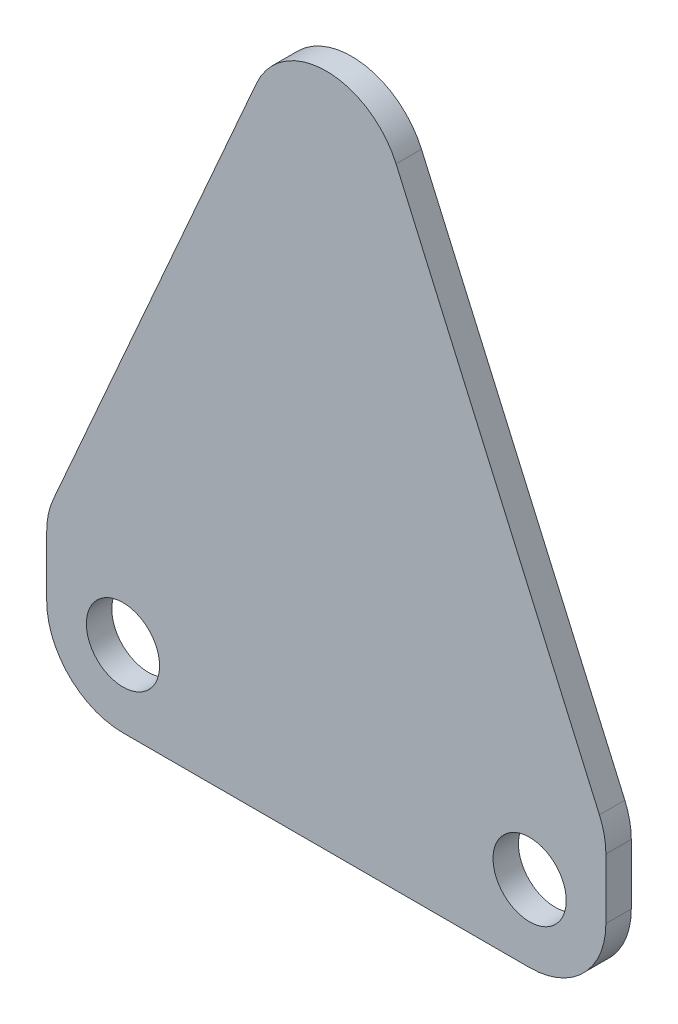
SolidWorks part; units mm, degrees
ref_plane "Front Plane" through (0, 0, 0) normal (0, 0, 1) x (1, 0, 0)
ref_plane "Top Plane" through (0, 0, 0) normal (0, 1, 0) x (1, 0, 0)
ref_plane "Right Plane" through (0, 0, 0) normal (1, 0, 0) x (0, 0, -1)
sketch "Sketch1" plane through (0, 0, 0) normal (0, 0, 1) x (1, 0, 0)
  line L0 (-17.4625, 0) -> (17.4625, 0)
  line L1 (17.4625, 0) -> (17.4625, 9.525)
  line L2 (17.4625, 9.525) -> (0, 49.2125)
  line L3 (0, 49.2125) -> (-17.4625, 9.525)
  line L4 (-17.4625, 9.525) -> (-17.4625, 0)
  line L5 (-12.7, 4.7625) -> (12.7, 4.7625) construction
  circle A0 centre (-12.7, 4.7625) radius 2.286
  circle A1 centre (12.7, 4.7625) radius 2.286
  point P4 (0, 0)
  point P12 (0, 4.7625)
  dimension "D3" = 4.572
  dimension "D1" = 25.4
  dimension "D2" = 9.525
  dimension "D4" = 4.7625
  dimension "D5" = 4.7625
  dimension "D7" = 44.45
extrude "Boss-Extrude1" add sketch "Sketch1" along normal blind 1.5875
fillet "Fillet1" radius 4.7625 5 edges at (-17.4625, 0, 0.7937) (-17.4625, 9.525, 0.7937) (17.4625, 0, 0.7937) (0, 49.2125, 0.7937) (17.4625, 9.525, 0.7937)
ref_axis "Axis1" through (17.4625, 4.7625, 0) along (-1, 0, 0)
